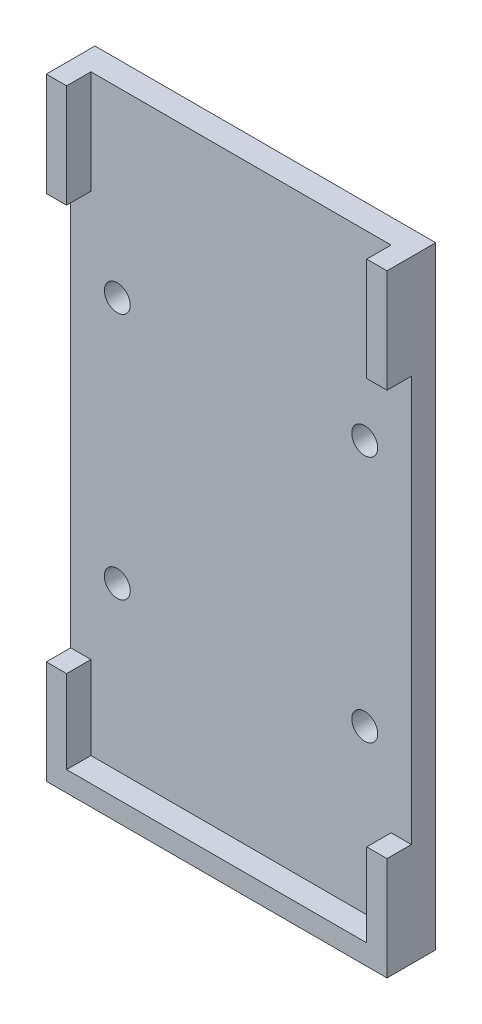
SolidWorks part; units mm, degrees
ref_plane "Front Plane" through (0, 0, 0) normal (0, 0, 1) x (1, 0, 0)
ref_plane "Top Plane" through (0, 0, 0) normal (0, 1, 0) x (1, 0, 0)
ref_plane "Right Plane" through (0, 0, 0) normal (1, 0, 0) x (0, 0, -1)
sketch "Sketch1" plane through (0, 0, 0) normal (0, 0, 1) x (1, 0, 0)
  line L1 (0, 0) -> (37, 0)
  line L2 (0, 0) -> (0, 73)
  line L4 (37, 0) -> (37, 73)
  dimension "D1" = 37
  dimension "D2" = 73
extrude "Extrude-Thin1" add sketch "Sketch1" along normal blind 3 thin thin type one direction reverse wall 2.5
sketch "Sketch2" plane through (0, 0, 0) normal (0, 0, -1) x (-1, 0, 0)
  line L0 (-39.5, 73) -> (2.5, 73)
  line L4 (0, 73) -> (0, 0)
  line L5 (-37, 73) -> (-39.5, 73)
  line L6 (-37, 0) -> (-37, 73)
  line L7 (0, 0) -> (-37, 0)
  line L17 (-39.5, 73) -> (-39.5, -2.5)
  line L18 (-39.5, 73) -> (-39.5, -2.5)
  line L19 (-39.5, -2.5) -> (2.5, -2.5)
  line L20 (-39.5, -2.5) -> (2.5, -2.5)
  line L21 (2.5, -2.5) -> (2.5, 73)
  line L22 (2.5, -2.5) -> (2.5, 73)
  line L23 (2.5, 73) -> (0, 73)
  dimension "D1" = 0
extrude "Boss-Extrude2" add sketch "Sketch2" along normal blind 3
sketch "Sketch3" plane through (0, 0, 0) normal (0, 0, 1) x (1, 0, 0)
  line L0 (18.5, -2.5) -> (18.5, 73) construction
  line L1 (39.5, -2.5) -> (-2.5, -2.5) construction
  line L2 (0, 73) -> (37, 73) construction
  line L3 (-2.5, 35.25) -> (39.5, 35.25) construction
  line L4 (-2.5, -2.5) -> (-2.5, 73) construction
  line L5 (39.5, 73) -> (39.5, -2.5) construction
  line L7 (33.75, 50.5) -> (3.25, 50.5) construction
  line L8 (33.75, 50.5) -> (33.75, 20) construction
  line L9 (33.75, 20) -> (3.25, 20) construction
  line L10 (3.25, 50.5) -> (3.25, 20) construction
  line L11 (33.75, 50.5) -> (3.25, 20) construction
  line L12 (33.75, 20) -> (3.25, 50.5) construction
  point P12 (18.5, 35.25)
  dimension "D1" = 30.5
  dimension "D2" = 30.5
hole_wizard "Ø3.2 (3.2) Diameter Hole1" positions "Sketch4" profile "Sketch5" hole size "Ø3.2" standard "ISO" end condition through all
sketch "Sketch4" plane through (0, 0, 0) normal (0, 0, 1) x (1, 0, 0)
  point P0 (3.25, 50.5)
  point P3 (33.75, 50.5)
  point P6 (33.75, 20)
  point P9 (3.25, 20)
sketch "Sketch5" plane through (3.25, 50.5, 0) normal (1, 0, 0) x (0, -1, 0)
  line L0 (0, 0) -> (0, 3)
  line L1 (0, 3) -> (1.6, 3)
  line L2 (1.6, 3) -> (1.6, 0)
  line L5 (1.6, 0) -> (0, 0)
  line L11 (0, -6.35) -> (0, 107.95) construction
  dimension "Thru Hole Dia." = 3.2
  dimension "Thru Hole Depth" = 3
sketch "Sketch6" plane through (0, 0, 3) normal (0, 0, 1) x (1, 0, 0)
  line L0 (-2.5, -2.5) -> (-2.5, 73) construction
  line L1 (-2.5, 10.25) -> (0, 10.25)
  line L2 (-2.5, 10.25) -> (-2.5, 60.25)
  line L3 (-2.5, 60.25) -> (0, 60.25)
  line L4 (0, 10.25) -> (0, 60.25)
  line L5 (0, 0) -> (0, 73) construction
  line L6 (-2.5, 35.25) -> (39.5, 35.25) construction
  point P9 (-2.5, 35.25)
  dimension "D1" = 50
extrude "Cut-Extrude1" cut sketch "Sketch6" against normal up to surface (3 mm away) up to face at (4.85, 50.5, 0)
ref_plane "Plane2" through (18.5, 0, 0) normal (1, 0, 0) x (0, 0, -1)
mirror "Mirror1" about plane through (18.5, 0, 0) normal (1, 0, 0) of "Cut-Extrude1"
